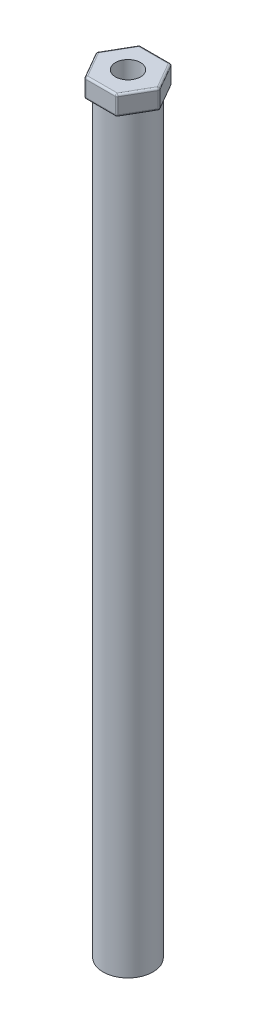
SolidWorks part; units mm, degrees
ref_plane "Front Plane" through (0, 0, 0) normal (0, 0, 1) x (1, 0, 0)
ref_plane "Top Plane" through (0, 0, 0) normal (0, 1, 0) x (1, 0, 0)
ref_plane "Right Plane" through (0, 0, 0) normal (1, 0, 0) x (0, 0, -1)
sketch "Sketch1" plane through (0, 0, 0) normal (0, 1, 0) x (1, 0, 0)
  circle A0 centre (0, 0) radius 6.35
  circle A1 centre (0, 0) radius 3.175
  dimension "D1" = 12.7
extrude "Boss-Extrude1" add sketch "Sketch1" along normal blind 190.5
ref_plane "Plane1" through (0, 95.25, 0) normal (0, 1, 0) x (1, 0, 0)
sketch "Sketch2" plane through (0, 190.5, 0) normal (0, 1, 0) x (1, 0, 0)
  line L1 (-8.0656, 0) -> (-4.0328, -6.985)
  line L2 (-4.0328, -6.985) -> (4.0328, -6.985)
  line L3 (4.0328, -6.985) -> (8.0656, 0)
  line L4 (8.0656, 0) -> (4.0328, 6.985)
  line L5 (4.0328, 6.985) -> (-4.0328, 6.985)
  line L6 (-4.0328, 6.985) -> (-8.0656, 0)
  circle A0 centre (0, 0) radius 6.985 construction
  circle A1 centre (0, 0) radius 3.175
  dimension "D1" = 13.97
extrude "Boss-Extrude2" add sketch "Sketch2" along normal blind 5
fillet "Fillet1" radius 0.5 18 edges at (6.0492, 190.5, -3.4925) (4.0328, 193, -6.985) (8.0656, 193, 0) (-4.0328, 193, -6.985) (-6.0492, 190.5, -3.4925) (-8.0656, 193, 0) (-6.0492, 190.5, 3.4925) (-4.0328, 193, 6.985) (0, 190.5, 6.985) (6.0492, 190.5, 3.4925) (4.0328, 193, 6.985) (6.0492, 195.5, 3.4925) (6.0492, 195.5, -3.4925) (0, 195.5, -6.985) (-6.0492, 195.5, -3.4925) (-6.0492, 195.5, 3.4925) (0, 195.5, 6.985) (0, 190.5, -6.985)
mirror "Mirror1" [suppressed] about plane through (0, 95.25, 0) normal (0, 1, 0)
